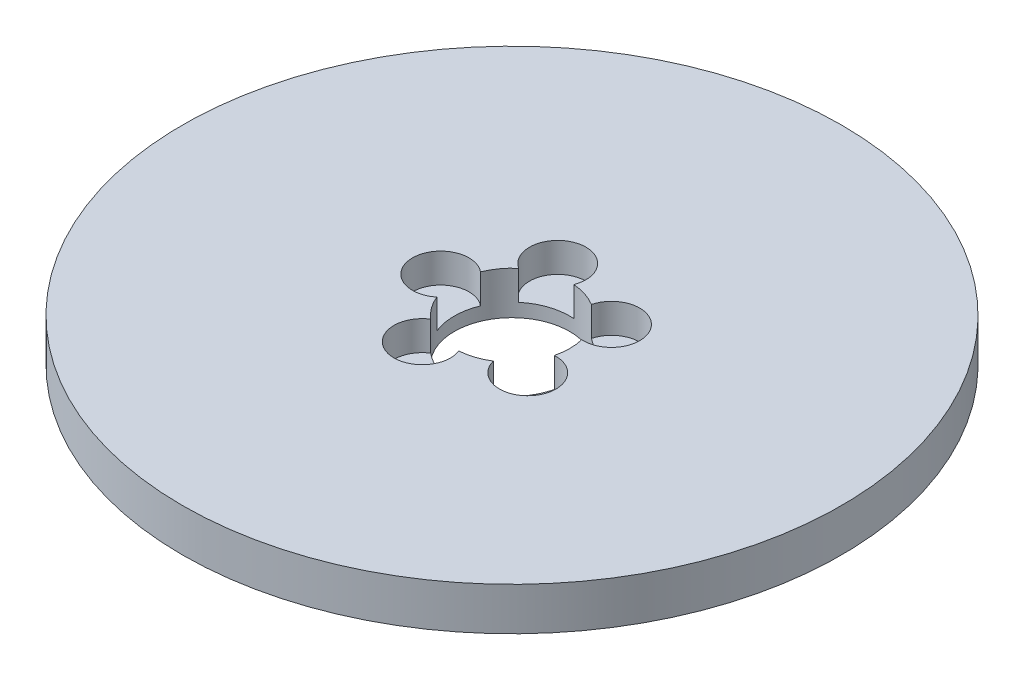
SolidWorks part; units mm, degrees
ref_plane "Front Plane" through (0, 0, 0) normal (0, 0, 1) x (1, 0, 0)
ref_plane "Top Plane" through (0, 0, 0) normal (0, 1, 0) x (1, 0, 0)
ref_plane "Right Plane" through (0, 0, 0) normal (1, 0, 0) x (0, 0, -1)
sketch "Sketch1" plane through (0, 0, 0) normal (0, 1, 0) x (1, 0, 0)
  circle A0 centre (0, 0) radius 100
  dimension "FLANGE_OD" = 200
extrude "Boss-Extrude1" add sketch "Sketch1" along normal blind 13
sketch "Sketch2" plane through (0, 0, 0) normal (0, 1, 0) x (1, 0, 0)
  circle A0 centre (0, 0) radius 17.5
  dimension "BORE_D" = 35
extrude "Cut-Extrude1" cut sketch "Sketch2" along normal through all
sketch "Sketch3" plane through (0, 13, 0) normal (0, 1, 0) x (1, 0, 0)
  circle A0 centre (0, 0) radius 21.6182 construction
  circle A1 centre (-21.6182, 0) radius 8.5701
  dimension "BOLT_D" = 17.1403
  dimension "BOLT_PCD" = 43.2363
extrude "Cut-Extrude2" cut sketch "Sketch3" against normal blind 8.9373
pattern_circular "CirPattern1" count 5 over 360 about axis through (0, 0, 0) along (0, 1, 0) of "Cut-Extrude2"
